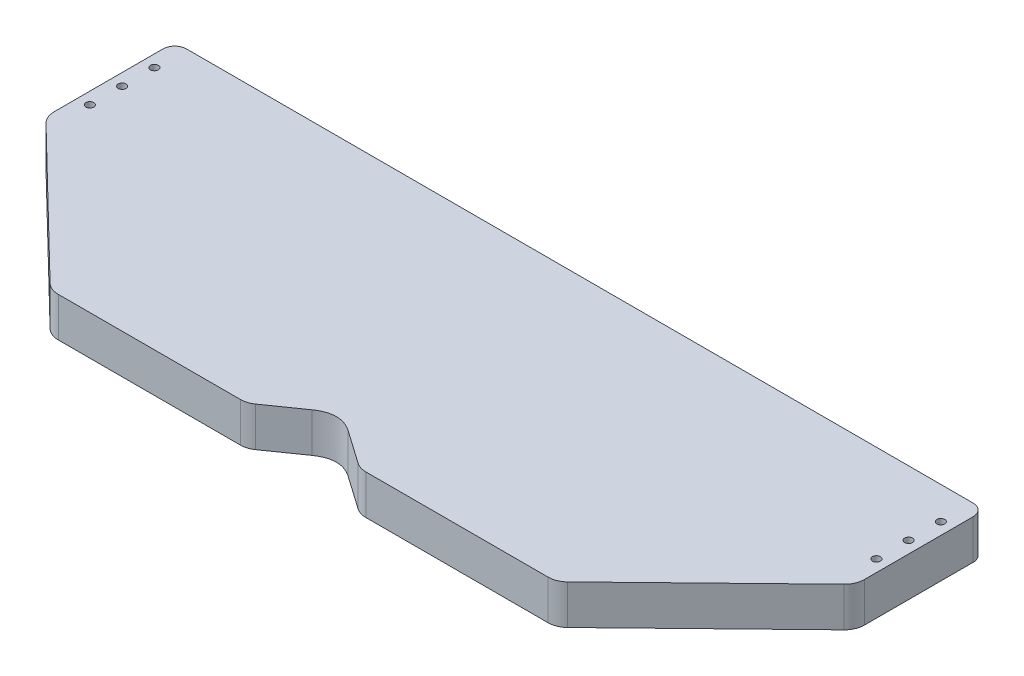
SolidWorks part; units mm, degrees
ref_plane "Front Plane" through (0, 0, 0) normal (0, 0, 1) x (1, 0, 0)
ref_plane "Top Plane" through (0, 0, 0) normal (0, 1, 0) x (1, 0, 0)
ref_plane "Right Plane" through (0, 0, 0) normal (1, 0, 0) x (0, 0, -1)
sketch "Sketch1" plane through (0, 0, 0) normal (0, 1, 0) x (1, 0, 0)
  line L0 (0, -60) -> (-14.2815, -70)
  line L1 (-14.2815, -70) -> (-64, -70)
  line L2 (-64, -70) -> (-102.5, -32.62)
  line L3 (-102.5, -32.62) -> (-102.5, 0)
  line L4 (-102.5, 0) -> (102.5, 0)
  line L5 (102.5, 0) -> (102.5, -32.62)
  line L6 (102.5, -32.62) -> (64, -70)
  line L7 (64, -70) -> (14.2815, -70)
  line L8 (14.2815, -70) -> (0, -60)
  line L9 (0, -55) -> (0, 55) construction
  circle A0 centre (99.5, -8.16) radius 1
  circle A1 centre (99.5, -16.32) radius 1
  circle A2 centre (99.5, -24.48) radius 1
  circle A3 centre (-99.5, -24.48) radius 1
  circle A4 centre (-99.5, -16.32) radius 1
  circle A5 centre (-99.5, -8.16) radius 1
  point P10 (0, 0)
  dimension "D7" = 3
  dimension "D8" = 2
  dimension "D1" = 70
  dimension "D2" = 10
  dimension "D3" = 35
  dimension "D4" = 205
  dimension "D5" = 128
  dimension "D9" = 8.16
  dimension "D11" = 8.16
  dimension "D12" = 32.62
  dimension "D10" = 3
extrude "Boss-Extrude1" add sketch "Sketch1" along normal mid plane 10
fillet "Fillet1" radius 5 2 edges at (14.2815, 0, 70) (-14.2815, 0, 70)
fillet "Fillet2" radius 5 2 edges at (-64, 0, 70) (64, 0, 70)
fillet "Fillet3" radius 5 2 edges at (-102.5, 0, 32.62) (102.5, 0, 32.62)
fillet "Fillet4" radius 3 2 edges at (102.5, 0, 0) (-102.5, 0, 0)
fillet "Fillet5" radius 8 1 edges at (0, 0, 60) conic rho 0.5
